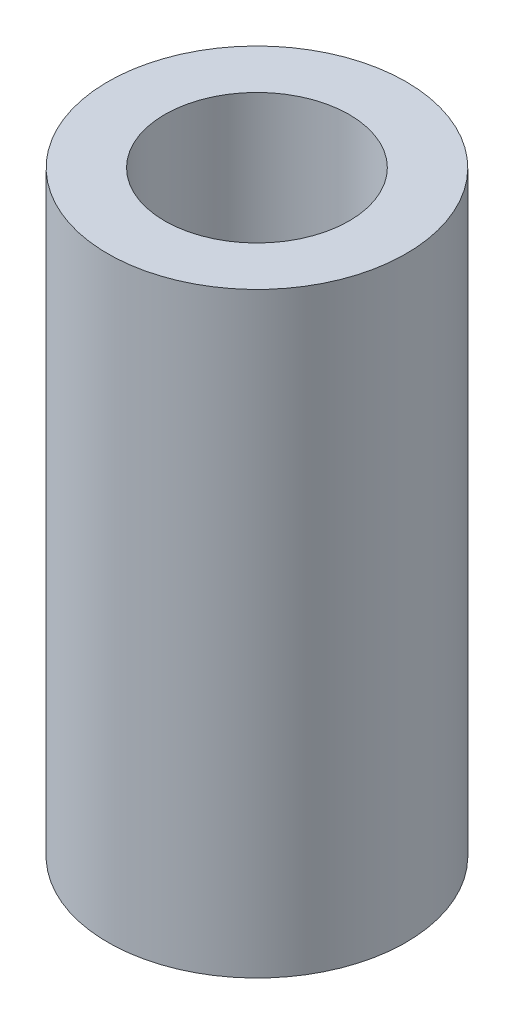
SolidWorks part; units mm, degrees
ref_plane "Front Plane" through (0, 0, 0) normal (0, 0, 1) x (1, 0, 0)
ref_plane "Top Plane" through (0, 0, 0) normal (0, 1, 0) x (1, 0, 0)
ref_plane "Right Plane" through (0, 0, 0) normal (1, 0, 0) x (0, 0, -1)
sketch "Sketch1" plane through (0, 0, 0) normal (0, 1, 0) x (1, 0, 0)
  circle A0 centre (0, 0) radius 2.3813
  circle A1 centre (0, 0) radius 1.4732
  dimension "D1" = 4.7625
  dimension "D2" = 2.9464
extrude "Boss-Extrude1" add sketch "Sketch1" along normal blind 9.525
